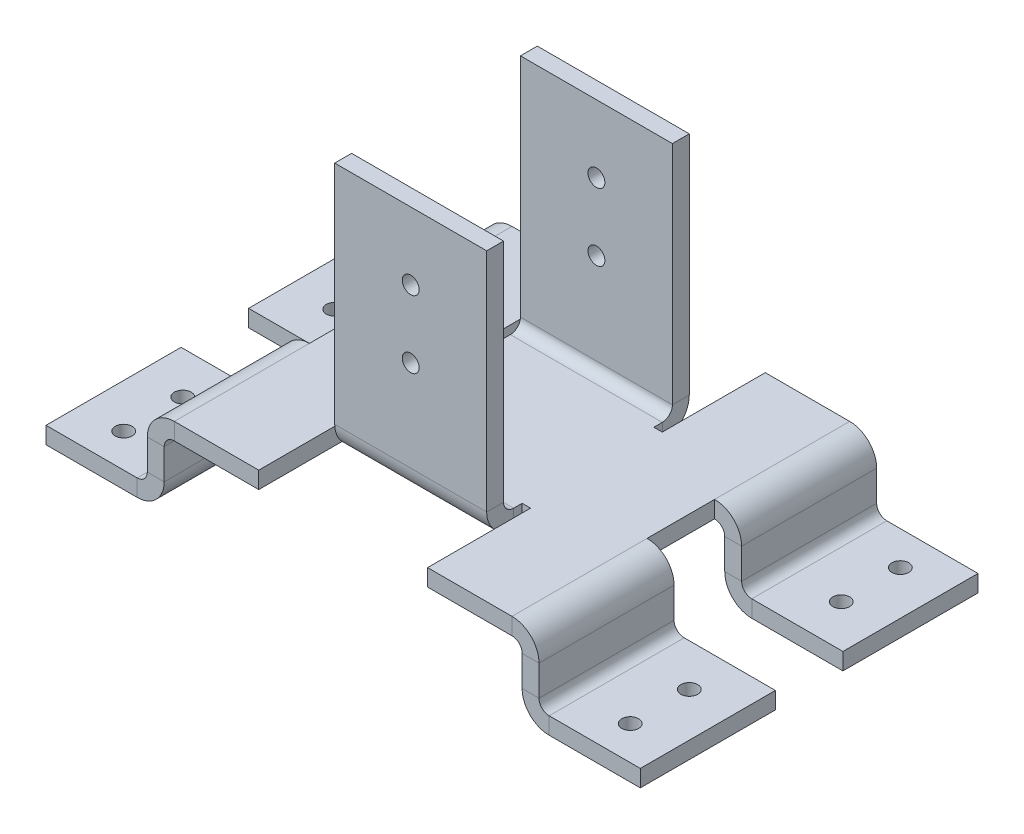
SolidWorks part; units mm, degrees
note: The reader was unsure of these and kept them because the rebuilt part matched: flange length of "边线-法兰1", "边线-法兰2", "边线-法兰14", "边线-法兰15", "边线-法兰16", "边线-法兰17", "边线-法兰18", "边线-法兰19", "边线-法兰20", "边线-法兰21".
ref_plane "前视基准面" through (0, 0, 0) normal (0, 0, 1) x (1, 0, 0)
ref_plane "上视基准面" through (0, 0, 0) normal (0, 1, 0) x (1, 0, 0)
ref_plane "右视基准面" through (0, 0, 0) normal (1, 0, 0) x (0, 0, -1)
other "Configuration Table"
sketch "草图1" plane through (0, 0, 0) normal (0, 1, 0) x (1, 0, 0)
  line L0 (-25, -25) -> (-25, -50)
  line L5 (-50, -50) -> (50, -50) construction
  line L6 (-50, -50) -> (-50, 50)
  line L11 (-50, 50) -> (50, 50) construction
  line L12 (50, -50) -> (50, 50)
  line L13 (-50, -50) -> (50, 50) construction
  line L14 (-50, 50) -> (50, -50) construction
  line L15 (-25, -25) -> (25, -25)
  line L16 (-25, -25) -> (-25, 25) construction
  line L17 (-25, 25) -> (25, 25)
  line L18 (25, -25) -> (25, 25) construction
  line L19 (-25, -25) -> (25, 25) construction
  line L20 (-25, 25) -> (25, -25) construction
  line L21 (-25, -50) -> (-50, -50)
  line L22 (25, -25) -> (25, -50)
  line L23 (25, -50) -> (50, -50)
  line L24 (-25, 25) -> (-25, 50)
  line L25 (-25, 50) -> (-50, 50)
  line L26 (25, 25) -> (25, 50)
  line L27 (25, 50) -> (50, 50)
  point P0 (0, 0)
  point P6 (0, 0)
  dimension "D1" = 100
  dimension "D2" = 100
  dimension "D3" = 50
base flange "基体-法兰1" sketch "草图1" thickness 5 reverse thickness direction no parameters "D1"=0.7366
edge flange "边线-法兰1" sketch "草图8" flange angle 90 flange length 75 flange position material outside bend radius 3 thickness 5 relief rectangular parameters "D6"=10
sketch "草图8" plane through (0, 0, -25) normal (0, 0, -1) x (-1, 0, 0)
  line L1 (-22.5, 0) -> (22.5, 0)
  line L2 (-22.5, 0) -> (-22.5, 70)
  line L3 (-22.5, 70) -> (22.5, 70)
  line L4 (22.5, 0) -> (22.5, 70)
  line L5 (-25, 0) -> (25, 0) construction
  point P6 (0, 70)
  dimension "D1" = 70
  dimension "D2" = 45
bend "边线折弯1" bend radius 3 bend angle 90 parameters "D5"=1
edge flange "边线-法兰2" sketch "草图11" flange angle 90 flange length 75 flange position material outside bend radius 3 thickness 5 relief rectangular parameters "D6"=10
sketch "草图11" plane through (0, 0, 25) normal (0, 0, 1) x (1, 0, 0)
  line L6 (-22.5, 70) -> (22.5, 70)
  line L7 (-22.5, 70) -> (-22.5, 0)
  line L8 (-22.5, 0) -> (22.5, 0)
  line L9 (22.5, 70) -> (22.5, 0)
bend "边线折弯2" bend radius 3 bend angle 90 parameters "D5"=2
edge flange "边线-法兰14" sketch "草图54" flange angle 90 flange length 25 flange position bend outside bend radius 3 thickness 5 relief rectangular parameters "D6"=10
sketch "草图54" plane through (50, -5, 0) normal (1, 0, 0) x (0, 0, 1)
  line L6 (50, 0) -> (10, 0)
  line L7 (50, 0) -> (50, 20)
  line L8 (50, 20) -> (10, 20)
  line L9 (10, 0) -> (10, 20)
  dimension "D1" = 20
  dimension "D2" = 40
bend "边线折弯12" bend radius 3 bend angle 90 parameters "D5"=3
edge flange "边线-法兰15" sketch "草图57" flange angle 90 flange length 25 flange position bend outside bend radius 3 thickness 5 relief rectangular parameters "D6"=10
sketch "草图57" plane through (50, -5, 0) normal (1, 0, 0) x (0, 0, 1)
  line L6 (-50, 0) -> (-10, 0)
  line L7 (-50, 0) -> (-50, 20)
  line L8 (-50, 20) -> (-10, 20)
  line L9 (-10, 0) -> (-10, 20)
  dimension "D1" = 40
  dimension "D2" = 20
bend "边线折弯13" bend radius 3 bend angle 90 parameters "D5"=4
edge flange "边线-法兰16" sketch "草图62" flange angle 90 flange length 25 flange position bend outside bend radius 3 thickness 5 relief rectangular parameters "D6"=10
sketch "草图62" plane through (-50, -5, 0) normal (-1, 0, 0) x (0, 0, -1)
  line L6 (50, 0) -> (10, 0)
  line L7 (50, 0) -> (50, 20)
  line L8 (50, 20) -> (10, 20)
  line L9 (10, 0) -> (10, 20)
bend "边线折弯14" bend radius 3 bend angle 90 parameters "D5"=5
edge flange "边线-法兰17" sketch "草图65" flange angle 90 flange length 25 flange position bend outside bend radius 3 thickness 5 relief rectangular parameters "D6"=10
sketch "草图65" plane through (-50, -5, 0) normal (-1, 0, 0) x (0, 0, -1)
  line L6 (-50, 0) -> (-10, 0)
  line L7 (-50, 0) -> (-50, 20)
  line L8 (-50, 20) -> (-10, 20)
  line L9 (-10, 0) -> (-10, 20)
bend "边线折弯15" bend radius 3 bend angle 90 parameters "D5"=6
edge flange "边线-法兰18" sketch "草图70" flange angle 90 flange length 35 bend radius 3 thickness 5 relief rectangular parameters "D6"=10
sketch "草图70" plane through (-58, -25, 0) normal (0, -1, 0) x (0, 0, 1)
  line L0 (-50, 0) -> (-10, 0) construction
  line L1 (-50, 0) -> (-10, 0)
  line L2 (-50, 0) -> (-50, 30)
  line L3 (-50, 30) -> (-10, 30)
  line L4 (-10, 30) -> (-10, 0)
  dimension "D1" = 30
bend "边线折弯16" bend radius 3 bend angle 90 parameters "D5"=7
edge flange "边线-法兰19" sketch "草图73" flange angle 90 flange length 35 bend radius 3 thickness 5 relief rectangular parameters "D6"=10
sketch "草图73" plane through (-58, -25, 0) normal (0, -1, 0) x (0, 0, 1)
  line L0 (10, 0) -> (50, 0) construction
  line L1 (10, 0) -> (50, 0)
  line L2 (10, 0) -> (10, 30)
  line L3 (10, 30) -> (50, 30)
  line L4 (50, 30) -> (50, 0)
  dimension "D1" = 30
bend "边线折弯17" bend radius 3 bend angle 90 parameters "D5"=8
edge flange "边线-法兰20" sketch "草图76" flange angle 90 flange length 35 bend radius 3 thickness 5 relief rectangular parameters "D6"=10
sketch "草图76" plane through (58, -25, 0) normal (0, -1, 0) x (0, 0, -1)
  line L0 (-50, 0) -> (-10, 0) construction
  line L1 (-50, 0) -> (-10, 0)
  line L2 (-50, 0) -> (-50, 30)
  line L3 (-50, 30) -> (-10, 30)
  line L4 (-10, 30) -> (-10, 0)
  dimension "D1" = 30
bend "边线折弯18" bend radius 3 bend angle 90 parameters "D5"=9
edge flange "边线-法兰21" sketch "草图79" flange angle 90 flange length 35 bend radius 3 thickness 5 relief rectangular parameters "D6"=10
sketch "草图79" plane through (58, -25, 0) normal (0, -1, 0) x (0, 0, -1)
  line L0 (10, 0) -> (50, 0) construction
  line L1 (10, 0) -> (50, 0)
  line L2 (10, 0) -> (10, 30)
  line L3 (10, 30) -> (50, 30)
  line L4 (50, 30) -> (50, 0)
  dimension "D1" = 30
bend "边线折弯19" bend radius 3 bend angle 90 parameters "D5"=10
sketch "草图80" plane through (0, 0, 0) normal (0, 1, 0) x (1, 0, 0)
  line L1 (-75, -40) -> (75, -40) construction
  line L2 (-75, -40) -> (-75, 40) construction
  line L3 (-75, 40) -> (75, 40) construction
  line L4 (75, -40) -> (75, 40) construction
  line L5 (-75, -40) -> (75, 40) construction
  line L6 (-75, 40) -> (75, -40) construction
  circle A0 centre (-75, 40) radius 2.5
  circle A1 centre (75, 40) radius 2.5
  circle A2 centre (-75, -40) radius 2.5
  circle A3 centre (75, -40) radius 2.5
  point P0 (0, 0)
  dimension "D3" = 5
  dimension "D4" = 5
  dimension "D5" = 5
  dimension "D6" = 5
  dimension "D1" = 80
  dimension "D2" = 150
extrude "切除-拉伸1" cut sketch "草图80" along normal up to surface (5 mm away) from surface at -25 up to face at (-74.5, -20, -30) starting at face at (-74.5, -25, -30)
sketch "草图83" plane through (0, 0, 0) normal (0, 0, 1) x (1, 0, 0)
  line L1 (-22.5, 70) -> (22.5, 70) construction
  line L2 (-22.5, 70) -> (-22.5, 10) construction
  line L3 (-22.5, 10) -> (22.5, 10) construction
  line L4 (22.5, 70) -> (22.5, 10) construction
  line L5 (-22.5, 70) -> (22.5, 10) construction
  line L6 (22.5, 70) -> (-22.5, 10) construction
  line L7 (0, 30) -> (0, 50) construction
  circle A0 centre (0, 50) radius 2.5
  circle A1 centre (0, 30) radius 2.5
  point P11 (0, 40)
  dimension "D3" = 5
  dimension "D4" = 5
  dimension "D1" = 60
  dimension "D2" = 20
extrude "切除-拉伸3" cut sketch "草图83" against normal through all and the other way through all normal cut yes
sketch "草图84" plane through (0, 0, 0) normal (0, 1, 0) x (1, 0, 0)
  line L1 (-75, -22.5) -> (75, -22.5) construction
  line L2 (-75, -22.5) -> (-75, 22.5) construction
  line L3 (-75, 22.5) -> (75, 22.5) construction
  line L4 (75, -22.5) -> (75, 22.5) construction
  line L5 (-75, -22.5) -> (75, 22.5) construction
  line L6 (-75, 22.5) -> (75, -22.5) construction
  circle A0 centre (75, 22.5) radius 2.5
  circle A1 centre (75, -22.5) radius 2.5
  circle A2 centre (-75, -22.5) radius 2.5
  circle A3 centre (-75, 22.5) radius 2.5
  point P0 (0, 0)
  dimension "D3" = 5
  dimension "D4" = 5
  dimension "D5" = 5
  dimension "D6" = 5
  dimension "D1" = 150
  dimension "D2" = 45
extrude "切除-拉伸5" cut sketch "草图84" against normal up to surface (5 mm away) from surface at -20 up to face at (-75, -25, 42.5) starting at face at (-75, -20, 42.5)
sketch "折弯-线1" plane through (0, 0, 0) normal (0, 1, 0) x (1, 0, 0)
sketch "边界框1" plane through (0, 0, 0) normal (0, 1, 0) x (1, 0, 0)
sheet metal parameters "钣金6" thickness 5 parameters "D1"=0.7366
flat pattern "平板型式6" [suppressed]
sketch "折弯-线2" plane through (0, 0, 0) normal (0, 1, 0) x (1, 0, 0)
sketch "边界框2" [suppressed] plane through (0, 0, 0) normal (0, 1, 0) x (1, 0, 0)
sheet metal parameters "钣金7" thickness 5 parameters "D1"=0.7366
flat pattern "平板型式6" [suppressed]
sketch "折弯-线2" plane through (0, 0, 0) normal (0, 1, 0) x (1, 0, 0)
sketch "边界框2" [suppressed] plane through (0, 0, 0) normal (0, 1, 0) x (1, 0, 0)
bend of the flat pattern "展平-<边线折弯1>1"
sheet metal parameters "钣金8" thickness 5 parameters "D1"=0.7366
flat pattern "平板型式6" [suppressed]
sketch "折弯-线2" plane through (0, 0, 0) normal (0, 1, 0) x (1, 0, 0)
sketch "边界框2" [suppressed] plane through (0, 0, 0) normal (0, 1, 0) x (1, 0, 0)
bend of the flat pattern "展平-<边线折弯1>1"
bend of the flat pattern "展平-<边线折弯2>1"
sheet metal parameters "钣金18" thickness 5 parameters "D1"=0.7366
flat pattern "平板型式6" [suppressed]
sketch "折弯-线2" plane through (0, 0, 0) normal (0, 1, 0) x (1, 0, 0)
sketch "边界框2" [suppressed] plane through (0, 0, 0) normal (0, 1, 0) x (1, 0, 0)
bend of the flat pattern "展平-<边线折弯1>1"
bend of the flat pattern "展平-<边线折弯2>1"
bend of the flat pattern "展平-<边线折弯12>1"
sheet metal parameters "钣金19" thickness 5 parameters "D1"=0.7366
flat pattern "平板型式6" [suppressed]
sketch "折弯-线2" plane through (0, 0, 0) normal (0, 1, 0) x (1, 0, 0)
sketch "边界框2" [suppressed] plane through (0, 0, 0) normal (0, 1, 0) x (1, 0, 0)
bend of the flat pattern "展平-<边线折弯1>1"
bend of the flat pattern "展平-<边线折弯2>1"
bend of the flat pattern "展平-<边线折弯13>1"
bend of the flat pattern "展平-<边线折弯12>1"
sheet metal parameters "钣金20" thickness 5 parameters "D1"=0.7366
flat pattern "平板型式6" [suppressed]
sketch "折弯-线2" plane through (0, 0, 0) normal (0, 1, 0) x (1, 0, 0)
sketch "边界框2" [suppressed] plane through (0, 0, 0) normal (0, 1, 0) x (1, 0, 0)
bend of the flat pattern "展平-<边线折弯1>1"
bend of the flat pattern "展平-<边线折弯2>1"
bend of the flat pattern "展平-<边线折弯13>1"
bend of the flat pattern "展平-<边线折弯14>1"
bend of the flat pattern "展平-<边线折弯12>1"
sheet metal parameters "钣金21" thickness 5 parameters "D1"=0.7366
flat pattern "平板型式6" [suppressed]
sketch "折弯-线2" plane through (0, 0, 0) normal (0, 1, 0) x (1, 0, 0)
sketch "边界框2" [suppressed] plane through (0, 0, 0) normal (0, 1, 0) x (1, 0, 0)
bend of the flat pattern "展平-<边线折弯1>1"
bend of the flat pattern "展平-<边线折弯2>1"
bend of the flat pattern "展平-<边线折弯13>1"
bend of the flat pattern "展平-<边线折弯14>1"
bend of the flat pattern "展平-<边线折弯15>1"
bend of the flat pattern "展平-<边线折弯12>1"
sheet metal parameters "钣金22" thickness 5 parameters "D1"=0.7366
flat pattern "平板型式6" [suppressed]
sketch "折弯-线2" plane through (0, 0, 0) normal (0, 1, 0) x (1, 0, 0)
sketch "边界框2" [suppressed] plane through (0, 0, 0) normal (0, 1, 0) x (1, 0, 0)
bend of the flat pattern "展平-<边线折弯1>1"
bend of the flat pattern "展平-<边线折弯2>1"
bend of the flat pattern "展平-<边线折弯13>1"
bend of the flat pattern "展平-<边线折弯14>1"
bend of the flat pattern "展平-<边线折弯15>1"
bend of the flat pattern "展平-<边线折弯12>1"
bend of the flat pattern "展平-<边线折弯16>1"
sheet metal parameters "钣金23" thickness 5 parameters "D1"=0.7366
flat pattern "平板型式6" [suppressed]
sketch "折弯-线2" plane through (0, 0, 0) normal (0, 1, 0) x (1, 0, 0)
sketch "边界框2" [suppressed] plane through (0, 0, 0) normal (0, 1, 0) x (1, 0, 0)
bend of the flat pattern "展平-<边线折弯1>1"
bend of the flat pattern "展平-<边线折弯2>1"
bend of the flat pattern "展平-<边线折弯13>1"
bend of the flat pattern "展平-<边线折弯14>1"
bend of the flat pattern "展平-<边线折弯15>1"
bend of the flat pattern "展平-<边线折弯12>1"
bend of the flat pattern "展平-<边线折弯17>1"
bend of the flat pattern "展平-<边线折弯16>1"
sheet metal parameters "钣金24" thickness 5 parameters "D1"=0.7366
flat pattern "平板型式6" [suppressed]
sketch "折弯-线2" plane through (0, 0, 0) normal (0, 1, 0) x (1, 0, 0)
sketch "边界框2" [suppressed] plane through (0, 0, 0) normal (0, 1, 0) x (1, 0, 0)
bend of the flat pattern "展平-<边线折弯1>1"
bend of the flat pattern "展平-<边线折弯2>1"
bend of the flat pattern "展平-<边线折弯13>1"
bend of the flat pattern "展平-<边线折弯14>1"
bend of the flat pattern "展平-<边线折弯15>1"
bend of the flat pattern "展平-<边线折弯12>1"
bend of the flat pattern "展平-<边线折弯17>1"
bend of the flat pattern "展平-<边线折弯18>1"
bend of the flat pattern "展平-<边线折弯16>1"
sheet metal parameters "钣金25" thickness 5 parameters "D1"=0.7366
flat pattern "平板型式6" [suppressed]
sketch "折弯-线2" plane through (0, 0, 0) normal (0, 1, 0) x (1, 0, 0)
sketch "边界框2" [suppressed] plane through (0, 0, 0) normal (0, 1, 0) x (1, 0, 0)
bend of the flat pattern "展平-<边线折弯1>1"
bend of the flat pattern "展平-<边线折弯2>1"
bend of the flat pattern "展平-<边线折弯13>1"
bend of the flat pattern "展平-<边线折弯14>1"
bend of the flat pattern "展平-<边线折弯15>1"
bend of the flat pattern "展平-<边线折弯12>1"
bend of the flat pattern "展平-<边线折弯17>1"
bend of the flat pattern "展平-<边线折弯18>1"
bend of the flat pattern "展平-<边线折弯19>1"
bend of the flat pattern "展平-<边线折弯16>1"
sheet metal parameters "钣金26" thickness 5 parameters "D1"=0.7366
flat pattern "平板型式6" [suppressed]
sketch "折弯-线2" plane through (0, 0, 0) normal (0, 1, 0) x (1, 0, 0)
sketch "边界框2" [suppressed] plane through (0, 0, 0) normal (0, 1, 0) x (1, 0, 0)
bend of the flat pattern "展平-<边线折弯1>1"
bend of the flat pattern "展平-<边线折弯2>1"
bend of the flat pattern "展平-<边线折弯13>1"
bend of the flat pattern "展平-<边线折弯14>1"
bend of the flat pattern "展平-<边线折弯15>1"
bend of the flat pattern "展平-<边线折弯12>1"
bend of the flat pattern "展平-<边线折弯17>1"
bend of the flat pattern "展平-<边线折弯18>1"
bend of the flat pattern "展平-<边线折弯19>1"
bend of the flat pattern "展平-<边线折弯16>1"
sheet metal parameters "钣金28" thickness 5 parameters "D1"=0.7366
flat pattern "平板型式6" [suppressed]
sketch "折弯-线2" plane through (0, 0, 0) normal (0, 1, 0) x (1, 0, 0)
sketch "边界框2" [suppressed] plane through (0, 0, 0) normal (0, 1, 0) x (1, 0, 0)
bend of the flat pattern "展平-<边线折弯1>1"
bend of the flat pattern "展平-<边线折弯2>1"
bend of the flat pattern "展平-<边线折弯13>1"
bend of the flat pattern "展平-<边线折弯14>1"
bend of the flat pattern "展平-<边线折弯15>1"
bend of the flat pattern "展平-<边线折弯12>1"
bend of the flat pattern "展平-<边线折弯17>1"
bend of the flat pattern "展平-<边线折弯18>1"
bend of the flat pattern "展平-<边线折弯19>1"
bend of the flat pattern "展平-<边线折弯16>1"
sheet metal parameters "钣金29" thickness 5 parameters "D1"=0.7366
flat pattern "平板型式6" [suppressed]
sketch "折弯-线2" plane through (0, 0, 0) normal (0, 1, 0) x (1, 0, 0)
sketch "边界框2" [suppressed] plane through (0, 0, 0) normal (0, 1, 0) x (1, 0, 0)
bend of the flat pattern "展平-<边线折弯1>1"
bend of the flat pattern "展平-<边线折弯2>1"
bend of the flat pattern "展平-<边线折弯13>1"
bend of the flat pattern "展平-<边线折弯14>1"
bend of the flat pattern "展平-<边线折弯15>1"
bend of the flat pattern "展平-<边线折弯12>1"
bend of the flat pattern "展平-<边线折弯17>1"
bend of the flat pattern "展平-<边线折弯18>1"
bend of the flat pattern "展平-<边线折弯19>1"
bend of the flat pattern "展平-<边线折弯16>1"
